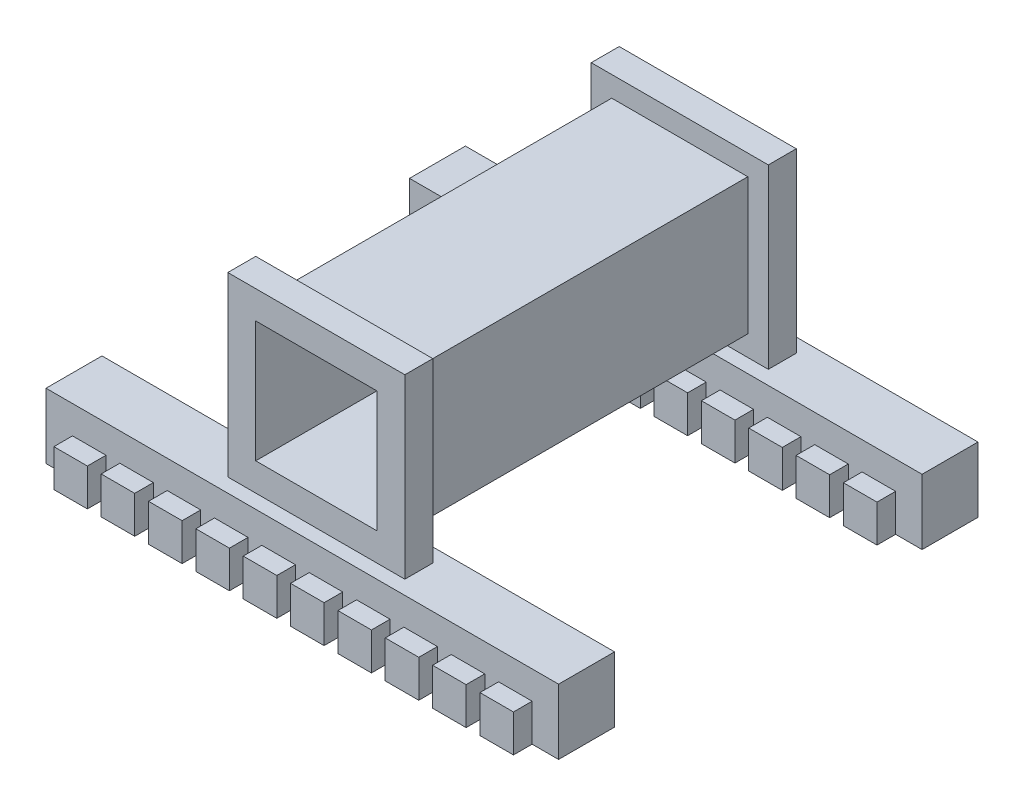
SolidWorks part; units mm, degrees
ref_plane "前视基准面" through (0, 0, 0) normal (0, 0, 1) x (1, 0, 0)
ref_plane "上视基准面" through (0, 0, 0) normal (0, 1, 0) x (1, 0, 0)
ref_plane "右视基准面" through (0, 0, 0) normal (1, 0, 0) x (0, 0, -1)
sketch "草图1" plane through (0, 0, 0) normal (0, 0, 1) x (1, 0, 0)
  line L0 (-9.5, 9.5) -> (9.5, 9.5)
  line L1 (-6.5, -6.5) -> (6.5, -6.5)
  line L2 (-6.5, -6.5) -> (-6.5, 6.5)
  line L3 (-6.5, 6.5) -> (6.5, 6.5)
  line L4 (6.5, -6.5) -> (6.5, 6.5)
  line L5 (-6.5, -6.5) -> (6.5, 6.5) construction
  line L6 (-6.5, 6.5) -> (6.5, -6.5) construction
  line L7 (9.5, -9.5) -> (9.5, 9.5)
  line L8 (-9.5, -9.5) -> (9.5, -9.5)
  line L9 (-9.5, -9.5) -> (-9.5, 9.5)
  line L10 (-7.3, 7.3) -> (7.3, 7.3)
  line L11 (7.3, -7.3) -> (7.3, 7.3)
  line L12 (-7.3, -7.3) -> (7.3, -7.3)
  line L13 (-7.3, -7.3) -> (-7.3, 7.3)
  line L15 (-27.5, -9.5) -> (27.5, -9.5)
  line L16 (-27.5, -9.5) -> (-27.5, -16.5)
  line L17 (-27.5, -16.5) -> (27.5, -16.5)
  line L18 (27.5, -9.5) -> (27.5, -16.5)
  point P0 (0, 0)
  dimension "D1" = 3
  dimension "D2" = 0.8
extrude "凸台-拉伸1" add sketch "草图1" along normal mid plane 42 contours L18 L15 L8 L16 L17 | L9 L8 L7 L0 L12 L13 L10 L11 | L13 L10 L11 L12 region at (0, 9.2313, 0) region at (0, -13, 0)
extrude "切除-拉伸1" cut sketch "草图1<3>" against normal mid plane 42 contours L2 L3 L4 L1
sketch "草图1<3>" plane through (0, 0, 0) normal (0, 0, 1) x (1, 0, 0) same geometry as "草图1"
sketch "草图2" plane through (0, 0, 0) normal (1, 0, 0) x (0, 0, -1)
  line L0 (21, -16.5) -> (21, -9.5) construction
  line L1 (21, -9.5) -> (-21, -9.5) construction
  line L2 (-21, -9.5) -> (-21, -16.5) construction
  line L3 (-21, -16.5) -> (21, -16.5) construction
  line L4 (21, -9.5) -> (21, 9.5) construction
  line L5 (21, 9.5) -> (-21, 9.5) construction
  line L6 (-21, 9.5) -> (-21, -9.5) construction
  line L7 (-21, -9.5) -> (21, -9.5) construction
  line L8 (21, -16.5) -> (21, -9.5)
  line L9 (21, -9.5) -> (-21, -9.5)
  line L10 (-21, -9.5) -> (-21, -16.5)
  line L11 (-21, -16.5) -> (21, -16.5)
  line L12 (21, -9.5) -> (21, 9.5)
  line L13 (21, 9.5) -> (-21, 9.5)
  line L14 (-21, 9.5) -> (-21, -9.5)
  line L15 (-21, -9.5) -> (21, -9.5)
extrude "切除-拉伸6" cut sketch "草图1<12>" against normal mid plane 36 contours L1 L4 L3 L2 | L9 L0 L7 L8 | L13 L10 L11 L12 region at (0, 0, 0)
sketch "草图1<12>" plane through (0, 0, 0) normal (0, 0, 1) x (1, 0, 0) same geometry as "草图1"
extrude "切除-拉伸7" cut sketch "草图1<13>" against normal mid plane 29 contours L18 L15 L8 L16 L17 region at (0, -13, 0)
sketch "草图1<13>" plane through (0, 0, 0) normal (0, 0, 1) x (1, 0, 0) same geometry as "草图1"
sketch "草图4" plane through (0, 0, 0) normal (1, 0, 0) x (0, 0, -1)
  line L0 (-21, -9.5) -> (-14.5, -9.5) construction
  line L1 (-14.5, -9.5) -> (-14.5, -16.5) construction
  line L2 (-14.5, -16.5) -> (-21, -16.5) construction
  line L3 (-21, -16.5) -> (-21, -9.5) construction
  line L4 (-18, 9.5) -> (-18, -9.5) construction
  line L5 (-18, -9.5) -> (-21, -9.5) construction
  line L6 (-21, -9.5) -> (-21, 9.5) construction
  line L7 (-21, 9.5) -> (-18, 9.5) construction
  line L8 (-18, -7.3) -> (-18, 7.3) construction
  line L9 (-18, 7.3) -> (18, 7.3) construction
  line L10 (18, 7.3) -> (18, -7.3) construction
  line L11 (18, -7.3) -> (-18, -7.3) construction
  line L12 (21, -9.5) -> (18, -9.5) construction
  line L13 (18, -9.5) -> (18, 9.5) construction
  line L14 (18, 9.5) -> (21, 9.5) construction
  line L15 (21, 9.5) -> (21, -9.5) construction
  line L16 (14.5, -16.5) -> (14.5, -9.5) construction
  line L17 (14.5, -9.5) -> (21, -9.5) construction
  line L18 (21, -9.5) -> (21, -16.5) construction
  line L19 (21, -16.5) -> (14.5, -16.5) construction
  line L20 (-21, -9.5) -> (-14.5, -9.5)
  line L21 (-14.5, -9.5) -> (-14.5, -16.5)
  line L22 (-14.5, -16.5) -> (-21, -16.5)
  line L23 (-21, -16.5) -> (-21, -9.5)
  line L24 (-18, 9.5) -> (-18, -9.5)
  line L25 (-18, -9.5) -> (-21, -9.5)
  line L26 (-21, -9.5) -> (-21, 9.5)
  line L27 (-21, 9.5) -> (-18, 9.5)
  line L28 (-18, -7.3) -> (-18, 7.3)
  line L29 (-18, 7.3) -> (18, 7.3)
  line L30 (18, 7.3) -> (18, -7.3)
  line L31 (18, -7.3) -> (-18, -7.3)
  line L32 (21, -9.5) -> (18, -9.5)
  line L33 (18, -9.5) -> (18, 9.5)
  line L34 (18, 9.5) -> (21, 9.5)
  line L35 (21, 9.5) -> (21, -9.5)
  line L36 (14.5, -16.5) -> (14.5, -9.5)
  line L37 (14.5, -9.5) -> (21, -9.5)
  line L38 (21, -9.5) -> (21, -16.5)
  line L39 (21, -16.5) -> (14.5, -16.5)
  line L40 (21, -9.5) -> (24.5, -9.5)
  line L41 (24.5, -9.5) -> (24.5, -16.5)
  line L42 (24.5, -16.5) -> (21, -16.5)
  line L43 (-21, -16.5) -> (-24.5049, -16.5)
  line L44 (-24.5049, -16.5) -> (-24.5049, -9.5)
  line L45 (-24.5049, -9.5) -> (-21, -9.5)
extrude "凸台-拉伸2" add sketch "草图4" along normal mid plane 55 contours L42 L41 L40 L38 | L45 L44 L43 L23 region at (0, -13, 22.7525) region at (0, -13, -22.75)
sketch "草图5" plane through (0, 0, -24.5) normal (0, 0, -1) x (-1, 0, 0)
  line L0 (-27.5, -16.5) -> (-22.86, -16.5)
  line L1 (-22.86, -16.5) -> (-22.86, -12.5036)
  line L3 (-17.78, -12.5036) -> (-17.78, -16.5)
  line L4 (27.5, -16.5) -> (27.5, -9.5)
  line L5 (27.5, -9.5) -> (-27.5, -9.5)
  line L6 (-27.5, -9.5) -> (-27.5, -16.5)
  line L7 (-27.5, -16.5) -> (27.5, -16.5)
  line L8 (27.5, -16.5) -> (27.5, -9.5)
  line L9 (27.5, -9.5) -> (-27.5, -9.5)
  line L10 (-27.5, -9.5) -> (-27.5, -16.5)
  line L12 (-9.5, -9.5) -> (9.5, -9.5)
  line L13 (-9.5, 9.5) -> (-9.5, -9.5)
  line L14 (9.5, 9.5) -> (-9.5, 9.5)
  line L15 (9.5, -9.5) -> (9.5, 9.5)
  line L16 (-9.5, -9.5) -> (9.5, -9.5)
  line L17 (-9.5, 9.5) -> (-9.5, -9.5)
  line L18 (9.5, 9.5) -> (-9.5, 9.5)
  line L19 (9.5, -9.5) -> (9.5, 9.5)
  line L20 (-17.78, -16.5) -> (-12.7, -16.5)
  line L21 (-12.7, -16.5) -> (-12.7, -12.5036)
  line L23 (-7.62, -12.5036) -> (-7.62, -16.5)
  line L24 (-27.5, -16.5) -> (27.5, -16.5) construction
  line L25 (-7.62, -16.5) -> (-2.54, -16.5)
  line L26 (-2.54, -16.5) -> (-2.54, -12.5186)
  line L28 (2.536, -12.5186) -> (2.536, -16.5)
  line L29 (2.536, -16.5) -> (7.62, -16.5)
  line L30 (7.62, -16.5) -> (7.62, -12.5078)
  line L32 (12.6981, -12.5078) -> (12.6981, -16.5)
  line L33 (12.6981, -16.5) -> (17.7801, -16.5)
  line L34 (17.7801, -16.5) -> (17.7801, -12.5082)
  line L36 (22.8591, -12.5082) -> (22.8591, -16.5)
  line L37 (22.8591, -16.5) -> (27.5, -16.5)
  line L39 (-21.06, -16.5) -> (-24.66, -16.5)
  line L40 (-21.06, -16.5) -> (-21.06, -12.5036)
  line L41 (-21.06, -12.5036) -> (-24.66, -12.5036)
  line L42 (-24.66, -16.5) -> (-24.66, -12.5036)
  line L43 (-21.06, -16.5) -> (-24.66, -12.5036) construction
  line L44 (-21.06, -12.5036) -> (-24.66, -16.5) construction
  line L45 (-15.98, -16.5) -> (-19.58, -16.5)
  line L46 (-15.98, -16.5) -> (-15.98, -12.5036)
  line L47 (-15.98, -12.5036) -> (-19.58, -12.5036)
  line L48 (-19.58, -16.5) -> (-19.58, -12.5036)
  line L49 (-15.98, -16.5) -> (-19.58, -12.5036) construction
  line L50 (-15.98, -12.5036) -> (-19.58, -16.5) construction
  line L51 (-10.9, -16.5) -> (-14.5, -16.5)
  line L52 (-10.9, -16.5) -> (-10.9, -12.5036)
  line L53 (-10.9, -12.5036) -> (-14.5, -12.5036)
  line L54 (-14.5, -16.5) -> (-14.5, -12.5036)
  line L55 (-10.9, -16.5) -> (-14.5, -12.5036) construction
  line L56 (-10.9, -12.5036) -> (-14.5, -16.5) construction
  line L57 (-5.82, -12.5036) -> (-9.42, -12.5036)
  line L58 (-5.82, -12.5036) -> (-5.82, -16.5)
  line L59 (-5.82, -16.5) -> (-9.42, -16.5)
  line L60 (-9.42, -12.5036) -> (-9.42, -16.5)
  line L61 (-5.82, -12.5036) -> (-9.42, -16.5) construction
  line L62 (-5.82, -16.5) -> (-9.42, -12.5036) construction
  line L63 (-0.74, -16.5075) -> (-4.34, -16.5075)
  line L64 (-0.74, -16.5075) -> (-0.74, -12.5111)
  line L65 (-0.74, -12.5111) -> (-4.34, -12.5111)
  line L66 (-4.34, -16.5075) -> (-4.34, -12.5111)
  line L67 (-0.74, -16.5075) -> (-4.34, -12.5111) construction
  line L68 (-0.74, -12.5111) -> (-4.34, -16.5075) construction
  line L69 (4.34, -16.5) -> (0.732, -16.5)
  line L70 (4.34, -16.5) -> (4.34, -12.5186)
  line L71 (4.34, -12.5186) -> (0.732, -12.5186)
  line L72 (0.732, -16.5) -> (0.732, -12.5186)
  line L73 (4.34, -16.5) -> (0.732, -12.5186) construction
  line L74 (4.34, -12.5186) -> (0.732, -16.5) construction
  line L75 (9.42, -16.4871) -> (5.82, -16.4871)
  line L76 (9.42, -16.4871) -> (9.42, -12.5206)
  line L77 (9.42, -12.5206) -> (5.82, -12.5206)
  line L78 (5.82, -16.4871) -> (5.82, -12.5206)
  line L79 (9.42, -16.4871) -> (5.82, -12.5206) construction
  line L80 (9.42, -12.5206) -> (5.82, -16.4871) construction
  line L81 (14.5, -16.5) -> (10.8963, -16.5)
  line L82 (14.5, -16.5) -> (14.5, -12.5078)
  line L83 (14.5, -12.5078) -> (10.8963, -12.5078)
  line L84 (10.8963, -16.5) -> (10.8963, -12.5078)
  line L85 (14.5, -16.5) -> (10.8963, -12.5078) construction
  line L86 (14.5, -12.5078) -> (10.8963, -16.5) construction
  line L87 (15.98, -16.5) -> (19.5801, -16.5)
  line L88 (15.98, -16.5) -> (15.98, -12.5082)
  line L89 (15.98, -12.5082) -> (19.5801, -12.5082)
  line L90 (19.5801, -16.5) -> (19.5801, -12.5082)
  line L91 (15.98, -16.5) -> (19.5801, -12.5082) construction
  line L92 (15.98, -12.5082) -> (19.5801, -16.5) construction
  line L93 (24.6583, -16.5) -> (21.06, -16.5)
  line L94 (24.6583, -16.5) -> (24.6583, -12.5082)
  line L95 (24.6583, -12.5082) -> (21.06, -12.5082)
  line L96 (21.06, -16.5) -> (21.06, -12.5082)
  line L97 (24.6583, -16.5) -> (21.06, -12.5082) construction
  line L98 (24.6583, -12.5082) -> (21.06, -16.5) construction
  point P6 (-22.86, -14.5018)
  point P35 (-17.78, -14.5018)
  point P40 (-12.7, -14.5018)
  point P45 (-7.62, -14.5018)
  point P50 (-2.54, -14.5093)
  point P55 (2.536, -14.5093)
  point P60 (7.62, -14.5039)
  point P65 (12.6981, -14.5039)
  point P70 (17.7801, -14.5041)
  point P75 (22.8591, -14.5041)
  line M42 (27.5, -16.5) -> (27.5, -9.5)
  line M43 (27.5, -9.5) -> (-27.5, -9.5)
  line M44 (-27.5, -9.5) -> (-27.5, -16.5)
  line M45 (-27.5, -16.5) -> (27.5, -16.5)
  dimension "D1" = 0
  dimension "D2" = 0
extrude "切除-拉伸9" cut sketch "草图5" against normal blind 2 contours L96 L95 L94 L37 L9 L42 L41 L40 L48 L47 L46 L20 L54 L53 L52 L60 L57 L58 L25 L66 L65 L64 L72 L71 L70 L29 L75 L78 L77 L76 M45 M42 M43 M44 region at (-0.0071, -12.1047, -24.5)
sketch "草图7" plane through (0, 0, 14.5) normal (0, 0, -1) x (-1, 0, 0)
  line L0 (21.06, -16.5) -> (24.6583, -16.5) construction
  line L1 (24.6583, -16.5) -> (24.6583, -12.5082) construction
  line L2 (24.6583, -12.5082) -> (21.06, -12.5082) construction
  line L3 (21.06, -12.5082) -> (21.06, -16.5) construction
  line L4 (15.98, -16.5) -> (19.5801, -16.5) construction
  line L5 (19.5801, -16.5) -> (19.5801, -12.5082) construction
  line L6 (19.5801, -12.5082) -> (15.98, -12.5082) construction
  line L7 (15.98, -12.5082) -> (15.98, -16.5) construction
  line L8 (10.8963, -16.5) -> (14.5, -16.5) construction
  line L9 (14.5, -16.5) -> (14.5, -12.5078) construction
  line L10 (14.5, -12.5078) -> (10.8963, -12.5078) construction
  line L11 (10.8963, -12.5078) -> (10.8963, -16.5) construction
  line L12 (5.82, -16.4871) -> (9.42, -16.4871) construction
  line L13 (9.42, -16.4871) -> (9.42, -12.5206) construction
  line L14 (9.42, -12.5206) -> (5.82, -12.5206) construction
  line L15 (5.82, -12.5206) -> (5.82, -16.4871) construction
  line L16 (0.732, -16.5) -> (4.34, -16.5) construction
  line L17 (4.34, -16.5) -> (4.34, -12.5186) construction
  line L18 (4.34, -12.5186) -> (0.732, -12.5186) construction
  line L19 (0.732, -12.5186) -> (0.732, -16.5) construction
  line L20 (-4.34, -16.5) -> (-0.74, -16.5) construction
  line L21 (-0.74, -16.5) -> (-0.74, -12.5111) construction
  line L22 (-0.74, -12.5111) -> (-4.34, -12.5111) construction
  line L23 (-4.34, -12.5111) -> (-4.34, -16.5) construction
  line L24 (-5.82, -16.5) -> (-5.82, -12.5036) construction
  line L25 (-5.82, -12.5036) -> (-9.42, -12.5036) construction
  line L26 (-9.42, -12.5036) -> (-9.42, -16.5) construction
  line L27 (-9.42, -16.5) -> (-5.82, -16.5) construction
  line L28 (-14.5, -16.5) -> (-10.9, -16.5) construction
  line L29 (-10.9, -16.5) -> (-10.9, -12.5036) construction
  line L30 (-10.9, -12.5036) -> (-14.5, -12.5036) construction
  line L31 (-14.5, -12.5036) -> (-14.5, -16.5) construction
  line L32 (-19.58, -16.5) -> (-15.98, -16.5) construction
  line L33 (-15.98, -16.5) -> (-15.98, -12.5036) construction
  line L34 (-15.98, -12.5036) -> (-19.58, -12.5036) construction
  line L35 (-19.58, -12.5036) -> (-19.58, -16.5) construction
  line L36 (-24.66, -16.5) -> (-21.06, -16.5) construction
  line L37 (-21.06, -16.5) -> (-21.06, -12.5036) construction
  line L38 (-21.06, -12.5036) -> (-24.66, -12.5036) construction
  line L39 (-24.66, -12.5036) -> (-24.66, -16.5) construction
  line L40 (21.06, -16.5) -> (24.6583, -16.5)
  line L41 (24.6583, -16.5) -> (24.6583, -12.5082)
  line L42 (24.6583, -12.5082) -> (21.06, -12.5082)
  line L43 (21.06, -12.5082) -> (21.06, -16.5)
  line L44 (15.98, -16.5) -> (19.5801, -16.5)
  line L45 (19.5801, -16.5) -> (19.5801, -12.5082)
  line L46 (19.5801, -12.5082) -> (15.98, -12.5082)
  line L47 (15.98, -12.5082) -> (15.98, -16.5)
  line L48 (10.8963, -16.5) -> (14.5, -16.5)
  line L49 (14.5, -16.5) -> (14.5, -12.5078)
  line L50 (14.5, -12.5078) -> (10.8963, -12.5078)
  line L51 (10.8963, -12.5078) -> (10.8963, -16.5)
  line L52 (5.82, -16.4871) -> (9.42, -16.4871)
  line L53 (9.42, -16.4871) -> (9.42, -12.5206)
  line L54 (9.42, -12.5206) -> (5.82, -12.5206)
  line L55 (5.82, -12.5206) -> (5.82, -16.4871)
  line L56 (0.732, -16.5) -> (4.34, -16.5)
  line L57 (4.34, -16.5) -> (4.34, -12.5186)
  line L58 (4.34, -12.5186) -> (0.732, -12.5186)
  line L59 (0.732, -12.5186) -> (0.732, -16.5)
  line L60 (-4.34, -16.5) -> (-0.74, -16.5)
  line L61 (-0.74, -16.5) -> (-0.74, -12.5111)
  line L62 (-0.74, -12.5111) -> (-4.34, -12.5111)
  line L63 (-4.34, -12.5111) -> (-4.34, -16.5)
  line L64 (-5.82, -16.5) -> (-5.82, -12.5036)
  line L65 (-5.82, -12.5036) -> (-9.42, -12.5036)
  line L66 (-9.42, -12.5036) -> (-9.42, -16.5)
  line L67 (-9.42, -16.5) -> (-5.82, -16.5)
  line L68 (-14.5, -16.5) -> (-10.9, -16.5)
  line L69 (-10.9, -16.5) -> (-10.9, -12.5036)
  line L70 (-10.9, -12.5036) -> (-14.5, -12.5036)
  line L71 (-14.5, -12.5036) -> (-14.5, -16.5)
  line L72 (-19.58, -16.5) -> (-15.98, -16.5)
  line L73 (-15.98, -16.5) -> (-15.98, -12.5036)
  line L74 (-15.98, -12.5036) -> (-19.58, -12.5036)
  line L75 (-19.58, -12.5036) -> (-19.58, -16.5)
  line L76 (-24.66, -16.5) -> (-21.06, -16.5)
  line L77 (-21.06, -16.5) -> (-21.06, -12.5036)
  line L78 (-21.06, -12.5036) -> (-24.66, -12.5036)
  line L79 (-24.66, -12.5036) -> (-24.66, -16.5)
  line L120 (19.5801, -16.5) -> (21.06, -16.5)
  line L121 (21.06, -16.5) -> (21.06, -12.5082)
  line L122 (21.06, -12.5082) -> (24.6583, -12.5082)
  line L123 (24.6583, -12.5082) -> (24.6583, -16.5)
  line L124 (24.6583, -16.5) -> (27.5, -16.5)
  line L125 (27.5, -16.5) -> (27.5, -9.5)
  line L126 (27.5, -9.5) -> (-27.5, -9.5)
  line L127 (-27.5, -9.5) -> (-27.5, -16.5)
  line L128 (-27.5, -16.5) -> (-24.66, -16.5)
  line L129 (-24.66, -16.5) -> (-24.66, -12.5036)
  line L130 (-24.66, -12.5036) -> (-21.06, -12.5036)
  line L131 (-21.06, -12.5036) -> (-21.06, -16.5)
  line L132 (-21.06, -16.5) -> (-19.58, -16.5)
  line L133 (-19.58, -16.5) -> (-19.58, -12.5036)
  line L134 (-19.58, -12.5036) -> (-15.98, -12.5036)
  line L135 (-15.98, -12.5036) -> (-15.98, -16.5)
  line L136 (-15.98, -16.5) -> (-14.5, -16.5)
  line L137 (-14.5, -16.5) -> (-14.5, -12.5036)
  line L138 (-14.5, -12.5036) -> (-10.9, -12.5036)
  line L139 (-10.9, -12.5036) -> (-10.9, -16.5)
  line L140 (-10.9, -16.5) -> (-9.42, -16.5)
  line L141 (-9.42, -16.5) -> (-9.42, -12.5036)
  line L142 (-9.42, -12.5036) -> (-5.82, -12.5036)
  line L143 (-5.82, -12.5036) -> (-5.82, -16.5)
  line L144 (-5.82, -16.5) -> (-4.34, -16.5)
  line L145 (-4.34, -16.5) -> (-4.34, -12.5111)
  line L146 (-4.34, -12.5111) -> (-0.74, -12.5111)
  line L147 (-0.74, -12.5111) -> (-0.74, -16.5)
  line L148 (-0.74, -16.5) -> (0.732, -16.5)
  line L149 (0.732, -16.5) -> (0.732, -12.5186)
  line L150 (0.732, -12.5186) -> (4.34, -12.5186)
  line L151 (4.34, -12.5186) -> (4.34, -16.5)
  line L152 (4.34, -16.5) -> (10.8963, -16.5)
  line L153 (10.8963, -16.5) -> (10.8963, -12.5078)
  line L154 (10.8963, -12.5078) -> (14.5, -12.5078)
  line L155 (14.5, -12.5078) -> (14.5, -16.5)
  line L156 (14.5, -16.5) -> (15.98, -16.5)
  line L157 (15.98, -16.5) -> (15.98, -12.5082)
  line L158 (15.98, -12.5082) -> (19.5801, -12.5082)
  line L159 (19.5801, -12.5082) -> (19.5801, -16.5)
  line L160 (19.5801, -16.5) -> (21.06, -16.5)
  line L161 (21.06, -16.5) -> (21.06, -12.5082)
  line L162 (21.06, -12.5082) -> (24.6583, -12.5082)
  line L163 (24.6583, -12.5082) -> (24.6583, -16.5)
  line L164 (24.6583, -16.5) -> (27.5, -16.5)
  line L165 (27.5, -16.5) -> (27.5, -9.5)
  line L166 (27.5, -9.5) -> (-27.5, -9.5)
  line L167 (-27.5, -9.5) -> (-27.5, -16.5)
  line L168 (-27.5, -16.5) -> (-24.66, -16.5)
  line L169 (-24.66, -16.5) -> (-24.66, -12.5036)
  line L170 (-24.66, -12.5036) -> (-21.06, -12.5036)
  line L171 (-21.06, -12.5036) -> (-21.06, -16.5)
  line L172 (-21.06, -16.5) -> (-19.58, -16.5)
  line L173 (-19.58, -16.5) -> (-19.58, -12.5036)
  line L174 (-19.58, -12.5036) -> (-15.98, -12.5036)
  line L175 (-15.98, -12.5036) -> (-15.98, -16.5)
  line L176 (-15.98, -16.5) -> (-14.5, -16.5)
  line L177 (-14.5, -16.5) -> (-14.5, -12.5036)
  line L178 (-14.5, -12.5036) -> (-10.9, -12.5036)
  line L179 (-10.9, -12.5036) -> (-10.9, -16.5)
  line L180 (-10.9, -16.5) -> (-9.42, -16.5)
  line L181 (-9.42, -16.5) -> (-9.42, -12.5036)
  line L182 (-9.42, -12.5036) -> (-5.82, -12.5036)
  line L183 (-5.82, -12.5036) -> (-5.82, -16.5)
  line L184 (-5.82, -16.5) -> (-4.34, -16.5)
  line L185 (-4.34, -16.5) -> (-4.34, -12.5111)
  line L186 (-4.34, -12.5111) -> (-0.74, -12.5111)
  line L187 (-0.74, -12.5111) -> (-0.74, -16.5)
  line L188 (-0.74, -16.5) -> (0.732, -16.5)
  line L189 (0.732, -16.5) -> (0.732, -12.5186)
  line L190 (0.732, -12.5186) -> (4.34, -12.5186)
  line L191 (4.34, -12.5186) -> (4.34, -16.5)
  line L192 (4.34, -16.5) -> (10.8963, -16.5)
  line L193 (10.8963, -16.5) -> (10.8963, -12.5078)
  line L194 (10.8963, -12.5078) -> (14.5, -12.5078)
  line L195 (14.5, -12.5078) -> (14.5, -16.5)
  line L196 (14.5, -16.5) -> (15.98, -16.5)
  line L197 (15.98, -16.5) -> (15.98, -12.5082)
  line L198 (15.98, -12.5082) -> (19.5801, -12.5082)
  line L199 (19.5801, -12.5082) -> (19.5801, -16.5)
  line M1 (-27.5, -9.5) -> (-27.5, -16.5)
  line M2 (-27.5, -16.5) -> (27.5, -16.5)
  line M3 (27.5, -16.5) -> (27.5, -9.5)
  line M4 (27.5, -9.5) -> (-27.5, -9.5)
  dimension "D1" = 0
extrude "切除-拉伸10" cut sketch "草图7" against normal blind 2 contours L79 L78 L77 L75 L74 L73 L71 L70 L69 L66 L65 L64 L63 L62 L61 L59 L58 L57 L51 L50 L49 L47 L46 L45 L43 L42 L41 L55 L54 L53 L52 M2 M3 M4 M1 region at (-0.0071, -12.1047, 14.5)
sketch "草图9" plane through (0, 0, -14.5) normal (0, 0, 1) x (1, 0, 0)
  line L0 (-4.34, -16.5) -> (-4.34, -12.5186) construction
  line L1 (-4.34, -12.5186) -> (-0.732, -12.5186) construction
  line L2 (-0.732, -12.5186) -> (-0.732, -16.5) construction
  line L3 (-0.732, -16.5) -> (-4.34, -16.5) construction
  line L4 (27.5, -16.5) -> (27.5, -9.5)
  line L5 (27.5, -9.5) -> (-27.5, -9.5)
  line L6 (-27.5, -9.5) -> (-27.5, -16.5)
  line L7 (-27.5, -16.5) -> (27.5, -16.5)
  line L8 (27.5, -16.5) -> (27.5, -9.5)
  line L9 (27.5, -9.5) -> (-27.5, -9.5)
  line L10 (-27.5, -9.5) -> (-27.5, -16.5)
  line L11 (-27.5, -16.5) -> (27.5, -16.5)
  line L12 (-5.82, -12.5206) -> (-5.82, -16.4871) construction
  line L13 (-5.82, -16.4871) -> (-9.42, -16.4871) construction
  line L14 (-9.42, -16.4871) -> (-9.42, -12.5206) construction
  line L15 (-9.42, -12.5206) -> (-5.82, -12.5206) construction
  line L16 (-14.5, -16.5) -> (-14.5, -12.5078) construction
  line L17 (-14.5, -12.5078) -> (-10.8963, -12.5078) construction
  line L18 (-10.8963, -12.5078) -> (-10.8963, -16.5) construction
  line L19 (-10.8963, -16.5) -> (-14.5, -16.5) construction
  line L20 (-19.5801, -16.5) -> (-19.5801, -12.5082) construction
  line L21 (-19.5801, -12.5082) -> (-15.98, -12.5082) construction
  line L22 (-15.98, -12.5082) -> (-15.98, -16.5) construction
  line L23 (-15.98, -16.5) -> (-19.5801, -16.5) construction
  line L24 (-24.6583, -16.5) -> (-24.6583, -12.5082) construction
  line L25 (-24.6583, -12.5082) -> (-21.06, -12.5082) construction
  line L26 (-21.06, -12.5082) -> (-21.06, -16.5) construction
  line L27 (-21.06, -16.5) -> (-24.6583, -16.5) construction
  line L28 (0.74, -16.5) -> (0.74, -12.5111) construction
  line L29 (0.74, -12.5111) -> (4.34, -12.5111) construction
  line L30 (4.34, -12.5111) -> (4.34, -16.5) construction
  line L31 (4.34, -16.5) -> (0.74, -16.5) construction
  line L32 (5.82, -16.5) -> (5.82, -12.5036) construction
  line L33 (5.82, -12.5036) -> (9.42, -12.5036) construction
  line L34 (9.42, -12.5036) -> (9.42, -16.5) construction
  line L35 (9.42, -16.5) -> (5.82, -16.5) construction
  line L36 (10.9, -16.5) -> (10.9, -12.5036) construction
  line L37 (10.9, -12.5036) -> (14.5, -12.5036) construction
  line L38 (14.5, -12.5036) -> (14.5, -16.5) construction
  line L39 (14.5, -16.5) -> (10.9, -16.5) construction
  line L40 (15.98, -16.5) -> (15.98, -12.5036) construction
  line L41 (15.98, -12.5036) -> (19.58, -12.5036) construction
  line L42 (19.58, -12.5036) -> (19.58, -16.5) construction
  line L43 (19.58, -16.5) -> (15.98, -16.5) construction
  line L44 (24.66, -12.5036) -> (24.66, -16.5) construction
  line L45 (24.66, -16.5) -> (21.06, -16.5) construction
  line L46 (21.06, -16.5) -> (21.06, -12.5036) construction
  line L47 (21.06, -12.5036) -> (24.66, -12.5036) construction
  line L48 (-4.34, -16.5) -> (-4.34, -12.5186)
  line L49 (-4.34, -12.5186) -> (-0.732, -12.5186)
  line L50 (-0.732, -12.5186) -> (-0.732, -16.5)
  line L51 (-0.732, -16.5) -> (-4.34, -16.5)
  line L52 (-5.82, -12.5206) -> (-5.82, -16.4871)
  line L53 (-5.82, -16.4871) -> (-9.42, -16.4871)
  line L54 (-9.42, -16.4871) -> (-9.42, -12.5206)
  line L55 (-9.42, -12.5206) -> (-5.82, -12.5206)
  line L56 (-14.5, -16.5) -> (-14.5, -12.5078)
  line L57 (-14.5, -12.5078) -> (-10.8963, -12.5078)
  line L58 (-10.8963, -12.5078) -> (-10.8963, -16.5)
  line L59 (-10.8963, -16.5) -> (-14.5, -16.5)
  line L60 (-19.5801, -16.5) -> (-19.5801, -12.5082)
  line L61 (-19.5801, -12.5082) -> (-15.98, -12.5082)
  line L62 (-15.98, -12.5082) -> (-15.98, -16.5)
  line L63 (-15.98, -16.5) -> (-19.5801, -16.5)
  line L64 (-24.6583, -16.5) -> (-24.6583, -12.5082)
  line L65 (-24.6583, -12.5082) -> (-21.06, -12.5082)
  line L66 (-21.06, -12.5082) -> (-21.06, -16.5)
  line L67 (-21.06, -16.5) -> (-24.6583, -16.5)
  line L68 (0.74, -16.5) -> (0.74, -12.5111)
  line L69 (0.74, -12.5111) -> (4.34, -12.5111)
  line L70 (4.34, -12.5111) -> (4.34, -16.5)
  line L71 (4.34, -16.5) -> (0.74, -16.5)
  line L72 (5.82, -16.5) -> (5.82, -12.5036)
  line L73 (5.82, -12.5036) -> (9.42, -12.5036)
  line L74 (9.42, -12.5036) -> (9.42, -16.5)
  line L75 (9.42, -16.5) -> (5.82, -16.5)
  line L76 (10.9, -16.5) -> (10.9, -12.5036)
  line L77 (10.9, -12.5036) -> (14.5, -12.5036)
  line L78 (14.5, -12.5036) -> (14.5, -16.5)
  line L79 (14.5, -16.5) -> (10.9, -16.5)
  line L80 (15.98, -16.5) -> (15.98, -12.5036)
  line L81 (15.98, -12.5036) -> (19.58, -12.5036)
  line L82 (19.58, -12.5036) -> (19.58, -16.5)
  line L83 (19.58, -16.5) -> (15.98, -16.5)
  line L84 (24.66, -12.5036) -> (24.66, -16.5)
  line L85 (24.66, -16.5) -> (21.06, -16.5)
  line L86 (21.06, -16.5) -> (21.06, -12.5036)
  line L87 (21.06, -12.5036) -> (24.66, -12.5036)
  line M5 (27.5, -16.5) -> (27.5, -9.5)
  line M6 (27.5, -9.5) -> (-27.5, -9.5)
  line M7 (-27.5, -9.5) -> (-27.5, -16.5)
  line M8 (-27.5, -16.5) -> (27.5, -16.5)
  dimension "D1" = 0
sketch "草图10" plane through (0, 0, 24.5049) normal (0, 0, 1) x (1, 0, 0)
  line L0 (-21.06, -16.5) -> (-24.6583, -16.5) construction
  line L1 (-24.6583, -16.5) -> (-24.6583, -12.5082) construction
  line L2 (-24.6583, -12.5082) -> (-21.06, -12.5082) construction
  line L3 (-21.06, -12.5082) -> (-21.06, -16.5) construction
  line L4 (-27.5, -9.5) -> (-27.5, -16.5)
  line L5 (-27.5, -16.5) -> (27.5, -16.5)
  line L6 (27.5, -16.5) -> (27.5, -9.5)
  line L7 (27.5, -9.5) -> (-27.5, -9.5)
  line L8 (-27.5, -9.5) -> (-27.5, -16.5)
  line L9 (-27.5, -16.5) -> (27.5, -16.5)
  line L10 (27.5, -16.5) -> (27.5, -9.5)
  line L11 (27.5, -9.5) -> (-27.5, -9.5)
  line L12 (-15.98, -16.5) -> (-19.5801, -16.5) construction
  line L13 (-19.5801, -16.5) -> (-19.5801, -12.5082) construction
  line L14 (-19.5801, -12.5082) -> (-15.98, -12.5082) construction
  line L15 (-15.98, -12.5082) -> (-15.98, -16.5) construction
  line L16 (-10.8963, -16.5) -> (-14.5, -16.5) construction
  line L17 (-14.5, -16.5) -> (-14.5, -12.5078) construction
  line L18 (-14.5, -12.5078) -> (-10.8963, -12.5078) construction
  line L19 (-10.8963, -12.5078) -> (-10.8963, -16.5) construction
  line L20 (-5.82, -16.4871) -> (-9.42, -16.4871) construction
  line L21 (-9.42, -16.4871) -> (-9.42, -12.5206) construction
  line L22 (-9.42, -12.5206) -> (-5.82, -12.5206) construction
  line L23 (-5.82, -12.5206) -> (-5.82, -16.4871) construction
  line L24 (-0.732, -16.5) -> (-4.34, -16.5) construction
  line L25 (-4.34, -16.5) -> (-4.34, -12.5186) construction
  line L26 (-4.34, -12.5186) -> (-0.732, -12.5186) construction
  line L27 (-0.732, -12.5186) -> (-0.732, -16.5) construction
  line L28 (4.34, -16.5) -> (0.74, -16.5) construction
  line L29 (0.74, -16.5) -> (0.74, -12.5111) construction
  line L30 (0.74, -12.5111) -> (4.34, -12.5111) construction
  line L31 (4.34, -12.5111) -> (4.34, -16.5) construction
  line L32 (5.82, -16.5) -> (5.82, -12.5036) construction
  line L33 (5.82, -12.5036) -> (9.42, -12.5036) construction
  line L34 (9.42, -12.5036) -> (9.42, -16.5) construction
  line L35 (9.42, -16.5) -> (5.82, -16.5) construction
  line L36 (14.5, -16.5) -> (10.9, -16.5) construction
  line L37 (10.9, -16.5) -> (10.9, -12.5036) construction
  line L38 (10.9, -12.5036) -> (14.5, -12.5036) construction
  line L39 (14.5, -12.5036) -> (14.5, -16.5) construction
  line L40 (19.58, -16.5) -> (15.98, -16.5) construction
  line L41 (15.98, -16.5) -> (15.98, -12.5036) construction
  line L42 (15.98, -12.5036) -> (19.58, -12.5036) construction
  line L43 (19.58, -12.5036) -> (19.58, -16.5) construction
  line L44 (24.66, -16.5) -> (21.06, -16.5) construction
  line L45 (21.06, -16.5) -> (21.06, -12.5036) construction
  line L46 (21.06, -12.5036) -> (24.66, -12.5036) construction
  line L47 (24.66, -12.5036) -> (24.66, -16.5) construction
  line L48 (-21.06, -16.5) -> (-24.6583, -16.5)
  line L49 (-24.6583, -16.5) -> (-24.6583, -12.5082)
  line L50 (-24.6583, -12.5082) -> (-21.06, -12.5082)
  line L51 (-21.06, -12.5082) -> (-21.06, -16.5)
  line L52 (-15.98, -16.5) -> (-19.5801, -16.5)
  line L53 (-19.5801, -16.5) -> (-19.5801, -12.5082)
  line L54 (-19.5801, -12.5082) -> (-15.98, -12.5082)
  line L55 (-15.98, -12.5082) -> (-15.98, -16.5)
  line L56 (-10.8963, -16.5) -> (-14.5, -16.5)
  line L57 (-14.5, -16.5) -> (-14.5, -12.5078)
  line L58 (-14.5, -12.5078) -> (-10.8963, -12.5078)
  line L59 (-10.8963, -12.5078) -> (-10.8963, -16.5)
  line L60 (-5.82, -16.4871) -> (-9.42, -16.4871)
  line L61 (-9.42, -16.4871) -> (-9.42, -12.5206)
  line L62 (-9.42, -12.5206) -> (-5.82, -12.5206)
  line L63 (-5.82, -12.5206) -> (-5.82, -16.4871)
  line L64 (-0.732, -16.5) -> (-4.34, -16.5)
  line L65 (-4.34, -16.5) -> (-4.34, -12.5186)
  line L66 (-4.34, -12.5186) -> (-0.732, -12.5186)
  line L67 (-0.732, -12.5186) -> (-0.732, -16.5)
  line L68 (4.34, -16.5) -> (0.74, -16.5)
  line L69 (0.74, -16.5) -> (0.74, -12.5111)
  line L70 (0.74, -12.5111) -> (4.34, -12.5111)
  line L71 (4.34, -12.5111) -> (4.34, -16.5)
  line L72 (5.82, -16.5) -> (5.82, -12.5036)
  line L73 (5.82, -12.5036) -> (9.42, -12.5036)
  line L74 (9.42, -12.5036) -> (9.42, -16.5)
  line L75 (9.42, -16.5) -> (5.82, -16.5)
  line L76 (14.5, -16.5) -> (10.9, -16.5)
  line L77 (10.9, -16.5) -> (10.9, -12.5036)
  line L78 (10.9, -12.5036) -> (14.5, -12.5036)
  line L79 (14.5, -12.5036) -> (14.5, -16.5)
  line L80 (19.58, -16.5) -> (15.98, -16.5)
  line L81 (15.98, -16.5) -> (15.98, -12.5036)
  line L82 (15.98, -12.5036) -> (19.58, -12.5036)
  line L83 (19.58, -12.5036) -> (19.58, -16.5)
  line L84 (24.66, -16.5) -> (21.06, -16.5)
  line L85 (21.06, -16.5) -> (21.06, -12.5036)
  line L86 (21.06, -12.5036) -> (24.66, -12.5036)
  line L87 (24.66, -12.5036) -> (24.66, -16.5)
  line M5 (-27.5, -9.5) -> (-27.5, -16.5)
  line M6 (-27.5, -16.5) -> (27.5, -16.5)
  line M7 (27.5, -16.5) -> (27.5, -9.5)
  line M8 (27.5, -9.5) -> (-27.5, -9.5)
  dimension "D1" = 0
extrude "切除-拉伸11" cut sketch "草图9" against normal blind 2 contours L86 L87 L84 L11 L64 L65 L66 L60 L61 L62 L56 L57 L58 L48 L49 L50 L68 L69 L70 L72 L73 L74 L76 L77 L78 L80 L81 L82 L54 L55 L52 L53 M5 M6 M7 M8 region at (-0.0071, -12.1047, -14.5)
extrude "切除-拉伸12" cut sketch "草图10" against normal blind 2 contours L86 L87 L49 L50 L51 L53 L54 L55 L57 L58 L59 L65 L66 L67 L69 L70 L71 L72 L73 L74 L77 L78 L79 L81 L82 L83 L85 L62 L63 L60 L61 M6 M7 M8 M5 region at (-0.0071, -12.1047, 24.5049)
sketch "草图11" plane through (0, -16.5, 0) normal (0, -1, 0) x (1, 0, 0)
  line L0 (-22.8591, 14.5) -> (-22.8591, 24.5049)
  line L1 (-17.7801, 14.5) -> (-17.7801, 24.5049)
  line L2 (-12.6981, 14.5) -> (-12.6981, 24.5049)
  line L3 (-7.62, 14.5) -> (-7.62, 24.5049)
  line L4 (-5.82, -14.5) -> (-9.42, -14.5)
  line L5 (-9.42, -14.5) -> (-9.42, -16.5)
  line L6 (-9.42, -16.5) -> (-5.82, -16.5)
  line L7 (-5.82, -16.5) -> (-5.82, -14.5)
  line L8 (-5.82, -14.5) -> (-9.42, -14.5)
  line L9 (-9.42, -14.5) -> (-9.42, -16.5)
  line L10 (-9.42, -16.5) -> (-5.82, -16.5)
  line L11 (-5.82, -16.5) -> (-5.82, -14.5)
  line L12 (-9.42, -24.5) -> (-5.82, -24.5)
  line L13 (-5.82, -24.5) -> (-5.82, -22.5)
  line L14 (-5.82, -22.5) -> (-9.42, -22.5)
  line L15 (-9.42, -22.5) -> (-9.42, -24.5)
  line L16 (-9.42, -24.5) -> (-5.82, -24.5)
  line L17 (-5.82, -24.5) -> (-5.82, -22.5)
  line L18 (-5.82, -22.5) -> (-9.42, -22.5)
  line L19 (-9.42, -22.5) -> (-9.42, -24.5)
  line L20 (-9.42, 14.5) -> (-5.82, 14.5)
  line L21 (-5.82, 14.5) -> (-5.82, 16.5)
  line L22 (-5.82, 16.5) -> (-9.42, 16.5)
  line L23 (-9.42, 16.5) -> (-9.42, 14.5)
  line L24 (-9.42, 14.5) -> (-5.82, 14.5)
  line L25 (-5.82, 14.5) -> (-5.82, 16.5)
  line L27 (-9.42, 16.5) -> (-9.42, 14.5)
  line L28 (-5.82, 24.5049) -> (-9.42, 24.5049)
  line L29 (-9.42, 24.5049) -> (-9.42, 22.5049)
  line L30 (-9.42, 22.5049) -> (-5.82, 22.5049)
  line L31 (-5.82, 22.5049) -> (-5.82, 24.5049)
  line L32 (-5.82, 24.5049) -> (-9.42, 24.5049)
  line L33 (-9.42, 24.5049) -> (-9.42, 22.5049)
  line L35 (-5.82, 22.5049) -> (-5.82, 24.5049)
  line L36 (-2.536, 14.5) -> (-2.536, 24.5049)
  line L37 (2.54, 14.5) -> (2.54, 24.5049)
  line L38 (7.62, 14.5) -> (7.62, 24.5049)
  line L39 (12.7, 14.5) -> (12.7, 24.5049)
  line L40 (17.78, 14.5) -> (17.78, 24.5049)
  line L41 (22.86, 14.5) -> (22.86, 24.5049)
  line L42 (22.86, -24.5) -> (22.86, -14.5)
  line L43 (17.78, -24.5) -> (17.78, -14.5)
  line L44 (12.7, -24.5) -> (12.7, -14.5)
  line L45 (2.54, -24.5) -> (2.54, -14.5)
  line L46 (7.62, -24.5) -> (7.62, -14.5)
  line L47 (-2.536, -24.5) -> (-2.536, -14.5)
  line L48 (-7.62, -24.5) -> (-7.62, -14.5)
  line L49 (-12.6981, -24.5) -> (-12.6981, -14.5)
  line L50 (-17.7801, -24.5) -> (-17.7801, -14.5)
  line L51 (-22.8591, -24.5) -> (-22.8591, -14.5)
  line L76 (-21.06, -14.5) -> (-24.6583, -14.5)
  line L77 (-24.6583, -14.5) -> (-24.6583, -16.5)
  line L78 (-24.6583, -16.5) -> (-27.5, -16.5)
  line L79 (-27.5, -16.5) -> (-27.5, -22.5)
  line L80 (-27.5, -22.5) -> (-24.6583, -22.5)
  line L81 (-24.6583, -22.5) -> (-24.6583, -24.5)
  line L82 (-24.6583, -24.5) -> (-21.06, -24.5)
  line L83 (-21.06, -24.5) -> (-21.06, -22.5)
  line L84 (-21.06, -22.5) -> (-19.5801, -22.5)
  line L85 (-19.5801, -22.5) -> (-19.5801, -24.5)
  line L86 (-19.5801, -24.5) -> (-15.98, -24.5)
  line L87 (-15.98, -24.5) -> (-15.98, -22.5)
  line L88 (-15.98, -22.5) -> (-14.5, -22.5)
  line L89 (-14.5, -22.5) -> (-14.5, -24.5)
  line L90 (-14.5, -24.5) -> (-10.8963, -24.5)
  line L91 (-10.8963, -24.5) -> (-10.8963, -22.5)
  line L92 (-10.8963, -22.5) -> (-4.34, -22.5)
  line L93 (-4.34, -22.5) -> (-4.34, -24.5)
  line L94 (-4.34, -24.5) -> (-0.732, -24.5)
  line L95 (-0.732, -24.5) -> (-0.732, -22.5)
  line L96 (-0.732, -22.5) -> (0.74, -22.5)
  line L97 (0.74, -22.5) -> (0.74, -24.5)
  line L98 (0.74, -24.5) -> (4.34, -24.5)
  line L99 (4.34, -24.5) -> (4.34, -22.5)
  line L100 (4.34, -22.5) -> (5.82, -22.5)
  line L101 (5.82, -22.5) -> (5.82, -24.5)
  line L102 (5.82, -24.5) -> (9.42, -24.5)
  line L103 (9.42, -24.5) -> (9.42, -22.5)
  line L104 (9.42, -22.5) -> (10.9, -22.5)
  line L105 (10.9, -22.5) -> (10.9, -24.5)
  line L106 (10.9, -24.5) -> (14.5, -24.5)
  line L107 (14.5, -24.5) -> (14.5, -22.5)
  line L108 (14.5, -22.5) -> (15.98, -22.5)
  line L109 (15.98, -22.5) -> (15.98, -24.5)
  line L110 (15.98, -24.5) -> (19.58, -24.5)
  line L111 (19.58, -24.5) -> (19.58, -22.5)
  line L112 (19.58, -22.5) -> (21.06, -22.5)
  line L113 (21.06, -22.5) -> (21.06, -24.5)
  line L114 (21.06, -24.5) -> (24.66, -24.5)
  line L115 (24.66, -24.5) -> (24.66, -22.5)
  line L116 (24.66, -22.5) -> (27.5, -22.5)
  line L117 (27.5, -22.5) -> (27.5, -16.5)
  line L118 (27.5, -16.5) -> (24.66, -16.5)
  line L119 (24.66, -16.5) -> (24.66, -14.5)
  line L120 (24.66, -14.5) -> (21.06, -14.5)
  line L121 (21.06, -14.5) -> (21.06, -16.5)
  line L122 (21.06, -16.5) -> (19.58, -16.5)
  line L123 (19.58, -16.5) -> (19.58, -14.5)
  line L124 (19.58, -14.5) -> (15.98, -14.5)
  line L125 (15.98, -14.5) -> (15.98, -16.5)
  line L126 (15.98, -16.5) -> (14.5, -16.5)
  line L127 (14.5, -16.5) -> (14.5, -14.5)
  line L128 (14.5, -14.5) -> (10.9, -14.5)
  line L129 (10.9, -14.5) -> (10.9, -16.5)
  line L130 (10.9, -16.5) -> (9.42, -16.5)
  line L131 (9.42, -16.5) -> (9.42, -14.5)
  line L132 (9.42, -14.5) -> (5.82, -14.5)
  line L133 (5.82, -14.5) -> (5.82, -16.5)
  line L134 (5.82, -16.5) -> (4.34, -16.5)
  line L135 (4.34, -16.5) -> (4.34, -14.5)
  line L136 (4.34, -14.5) -> (0.74, -14.5)
  line L137 (0.74, -14.5) -> (0.74, -16.5)
  line L138 (0.74, -16.5) -> (-0.732, -16.5)
  line L139 (-0.732, -16.5) -> (-0.732, -14.5)
  line L140 (-0.732, -14.5) -> (-4.34, -14.5)
  line L141 (-4.34, -14.5) -> (-4.34, -16.5)
  line L142 (-4.34, -16.5) -> (-10.8963, -16.5)
  line L143 (-10.8963, -16.5) -> (-10.8963, -14.5)
  line L144 (-10.8963, -14.5) -> (-14.5, -14.5)
  line L145 (-14.5, -14.5) -> (-14.5, -16.5)
  line L146 (-14.5, -16.5) -> (-15.98, -16.5)
  line L147 (-15.98, -16.5) -> (-15.98, -14.5)
  line L148 (-15.98, -14.5) -> (-19.5801, -14.5)
  line L149 (-19.5801, -14.5) -> (-19.5801, -16.5)
  line L150 (-19.5801, -16.5) -> (-21.06, -16.5)
  line L151 (-21.06, -16.5) -> (-21.06, -14.5)
  line L152 (-21.06, -14.5) -> (-24.6583, -14.5)
  line L153 (-24.6583, -14.5) -> (-24.6583, -16.5)
  line L154 (-24.6583, -16.5) -> (-27.5, -16.5)
  line L155 (-27.5, -16.5) -> (-27.5, -22.5)
  line L156 (-27.5, -22.5) -> (-24.6583, -22.5)
  line L157 (-24.6583, -22.5) -> (-24.6583, -24.5)
  line L158 (-24.6583, -24.5) -> (-21.06, -24.5)
  line L159 (-21.06, -24.5) -> (-21.06, -22.5)
  line L160 (-21.06, -22.5) -> (-19.5801, -22.5)
  line L161 (-19.5801, -22.5) -> (-19.5801, -24.5)
  line L162 (-19.5801, -24.5) -> (-15.98, -24.5)
  line L163 (-15.98, -24.5) -> (-15.98, -22.5)
  line L164 (-15.98, -22.5) -> (-14.5, -22.5)
  line L165 (-14.5, -22.5) -> (-14.5, -24.5)
  line L166 (-14.5, -24.5) -> (-10.8963, -24.5)
  line L167 (-10.8963, -24.5) -> (-10.8963, -22.5)
  line L168 (-10.8963, -22.5) -> (-4.34, -22.5)
  line L169 (-4.34, -22.5) -> (-4.34, -24.5)
  line L170 (-4.34, -24.5) -> (-0.732, -24.5)
  line L171 (-0.732, -24.5) -> (-0.732, -22.5)
  line L172 (-0.732, -22.5) -> (0.74, -22.5)
  line L173 (0.74, -22.5) -> (0.74, -24.5)
  line L174 (0.74, -24.5) -> (4.34, -24.5)
  line L175 (4.34, -24.5) -> (4.34, -22.5)
  line L176 (4.34, -22.5) -> (5.82, -22.5)
  line L177 (5.82, -22.5) -> (5.82, -24.5)
  line L178 (5.82, -24.5) -> (9.42, -24.5)
  line L179 (9.42, -24.5) -> (9.42, -22.5)
  line L180 (9.42, -22.5) -> (10.9, -22.5)
  line L181 (10.9, -22.5) -> (10.9, -24.5)
  line L182 (10.9, -24.5) -> (14.5, -24.5)
  line L183 (14.5, -24.5) -> (14.5, -22.5)
  line L184 (14.5, -22.5) -> (15.98, -22.5)
  line L185 (15.98, -22.5) -> (15.98, -24.5)
  line L186 (15.98, -24.5) -> (19.58, -24.5)
  line L187 (19.58, -24.5) -> (19.58, -22.5)
  line L188 (19.58, -22.5) -> (21.06, -22.5)
  line L189 (21.06, -22.5) -> (21.06, -24.5)
  line L190 (21.06, -24.5) -> (24.66, -24.5)
  line L191 (24.66, -24.5) -> (24.66, -22.5)
  line L192 (24.66, -22.5) -> (27.5, -22.5)
  line L193 (27.5, -22.5) -> (27.5, -16.5)
  line L194 (27.5, -16.5) -> (24.66, -16.5)
  line L195 (24.66, -16.5) -> (24.66, -14.5)
  line L196 (24.66, -14.5) -> (21.06, -14.5)
  line L197 (21.06, -14.5) -> (21.06, -16.5)
  line L198 (21.06, -16.5) -> (19.58, -16.5)
  line L199 (19.58, -16.5) -> (19.58, -14.5)
  line L200 (19.58, -14.5) -> (15.98, -14.5)
  line L201 (15.98, -14.5) -> (15.98, -16.5)
  line L202 (15.98, -16.5) -> (14.5, -16.5)
  line L203 (14.5, -16.5) -> (14.5, -14.5)
  line L204 (14.5, -14.5) -> (10.9, -14.5)
  line L205 (10.9, -14.5) -> (10.9, -16.5)
  line L206 (10.9, -16.5) -> (9.42, -16.5)
  line L207 (9.42, -16.5) -> (9.42, -14.5)
  line L208 (9.42, -14.5) -> (5.82, -14.5)
  line L209 (5.82, -14.5) -> (5.82, -16.5)
  line L210 (5.82, -16.5) -> (4.34, -16.5)
  line L211 (4.34, -16.5) -> (4.34, -14.5)
  line L212 (4.34, -14.5) -> (0.74, -14.5)
  line L213 (0.74, -14.5) -> (0.74, -16.5)
  line L214 (0.74, -16.5) -> (-0.732, -16.5)
  line L215 (-0.732, -16.5) -> (-0.732, -14.5)
  line L216 (-0.732, -14.5) -> (-4.34, -14.5)
  line L217 (-4.34, -14.5) -> (-4.34, -16.5)
  line L218 (-4.34, -16.5) -> (-10.8963, -16.5)
  line L219 (-10.8963, -16.5) -> (-10.8963, -14.5)
  line L220 (-10.8963, -14.5) -> (-14.5, -14.5)
  line L221 (-14.5, -14.5) -> (-14.5, -16.5)
  line L222 (-14.5, -16.5) -> (-15.98, -16.5)
  line L223 (-15.98, -16.5) -> (-15.98, -14.5)
  line L224 (-15.98, -14.5) -> (-19.5801, -14.5)
  line L225 (-19.5801, -14.5) -> (-19.5801, -16.5)
  line L226 (-19.5801, -16.5) -> (-21.06, -16.5)
  line L227 (-21.06, -16.5) -> (-21.06, -14.5)
  line L244 (-21.06, 24.5049) -> (-24.6583, 24.5049)
  line L245 (-24.6583, 24.5049) -> (-24.6583, 22.5049)
  line L246 (-24.6583, 22.5049) -> (-27.5, 22.5049)
  line L247 (-27.5, 22.5049) -> (-27.5, 16.5)
  line L248 (-27.5, 16.5) -> (-24.6583, 16.5)
  line L249 (-24.6583, 16.5) -> (-24.6583, 14.5)
  line L250 (-24.6583, 14.5) -> (-21.06, 14.5)
  line L251 (-21.06, 14.5) -> (-21.06, 16.5)
  line L252 (-21.06, 16.5) -> (-19.5801, 16.5)
  line L253 (-19.5801, 16.5) -> (-19.5801, 14.5)
  line L254 (-19.5801, 14.5) -> (-15.98, 14.5)
  line L255 (-15.98, 14.5) -> (-15.98, 16.5)
  line L256 (-15.98, 16.5) -> (-14.5, 16.5)
  line L257 (-14.5, 16.5) -> (-14.5, 14.5)
  line L258 (-14.5, 14.5) -> (-10.8963, 14.5)
  line L259 (-10.8963, 14.5) -> (-10.8963, 16.5)
  line L260 (-10.8963, 16.5) -> (-4.34, 16.5)
  line L261 (-4.34, 16.5) -> (-4.34, 14.5)
  line L262 (-4.34, 14.5) -> (-0.732, 14.5)
  line L263 (-0.732, 14.5) -> (-0.732, 16.5)
  line L264 (-0.732, 16.5) -> (0.74, 16.5)
  line L265 (0.74, 16.5) -> (0.74, 14.5)
  line L266 (0.74, 14.5) -> (4.34, 14.5)
  line L267 (4.34, 14.5) -> (4.34, 16.5)
  line L268 (4.34, 16.5) -> (5.82, 16.5)
  line L269 (5.82, 16.5) -> (5.82, 14.5)
  line L270 (5.82, 14.5) -> (9.42, 14.5)
  line L271 (9.42, 14.5) -> (9.42, 16.5)
  line L272 (9.42, 16.5) -> (10.9, 16.5)
  line L273 (10.9, 16.5) -> (10.9, 14.5)
  line L274 (10.9, 14.5) -> (14.5, 14.5)
  line L275 (14.5, 14.5) -> (14.5, 16.5)
  line L276 (14.5, 16.5) -> (15.98, 16.5)
  line L277 (15.98, 16.5) -> (15.98, 14.5)
  line L278 (15.98, 14.5) -> (19.58, 14.5)
  line L279 (19.58, 14.5) -> (19.58, 16.5)
  line L280 (19.58, 16.5) -> (21.06, 16.5)
  line L281 (21.06, 16.5) -> (21.06, 14.5)
  line L282 (21.06, 14.5) -> (24.66, 14.5)
  line L283 (24.66, 14.5) -> (24.66, 16.5)
  line L284 (24.66, 16.5) -> (27.5, 16.5)
  line L285 (27.5, 16.5) -> (27.5, 22.5049)
  line L286 (27.5, 22.5049) -> (24.66, 22.5049)
  line L287 (24.66, 22.5049) -> (24.66, 24.5049)
  line L288 (24.66, 24.5049) -> (21.06, 24.5049)
  line L289 (21.06, 24.5049) -> (21.06, 22.5049)
  line L290 (21.06, 22.5049) -> (19.58, 22.5049)
  line L291 (19.58, 22.5049) -> (19.58, 24.5049)
  line L292 (19.58, 24.5049) -> (15.98, 24.5049)
  line L293 (15.98, 24.5049) -> (15.98, 22.5049)
  line L294 (15.98, 22.5049) -> (14.5, 22.5049)
  line L295 (14.5, 22.5049) -> (14.5, 24.5049)
  line L296 (14.5, 24.5049) -> (10.9, 24.5049)
  line L297 (10.9, 24.5049) -> (10.9, 22.5049)
  line L298 (10.9, 22.5049) -> (9.42, 22.5049)
  line L299 (9.42, 22.5049) -> (9.42, 24.5049)
  line L300 (9.42, 24.5049) -> (5.82, 24.5049)
  line L301 (5.82, 24.5049) -> (5.82, 22.5049)
  line L302 (5.82, 22.5049) -> (4.34, 22.5049)
  line L303 (4.34, 22.5049) -> (4.34, 24.5049)
  line L304 (4.34, 24.5049) -> (0.74, 24.5049)
  line L305 (0.74, 24.5049) -> (0.74, 22.5049)
  line L306 (0.74, 22.5049) -> (-0.732, 22.5049)
  line L307 (-0.732, 22.5049) -> (-0.732, 24.5049)
  line L308 (-0.732, 24.5049) -> (-4.34, 24.5049)
  line L309 (-4.34, 24.5049) -> (-4.34, 22.5049)
  line L310 (-4.34, 22.5049) -> (-10.8963, 22.5049)
  line L311 (-10.8963, 22.5049) -> (-10.8963, 24.5049)
  line L312 (-10.8963, 24.5049) -> (-14.5, 24.5049)
  line L313 (-14.5, 24.5049) -> (-14.5, 22.5049)
  line L314 (-14.5, 22.5049) -> (-15.98, 22.5049)
  line L315 (-15.98, 22.5049) -> (-15.98, 24.5049)
  line L316 (-15.98, 24.5049) -> (-19.5801, 24.5049)
  line L317 (-19.5801, 24.5049) -> (-19.5801, 22.5049)
  line L318 (-19.5801, 22.5049) -> (-21.06, 22.5049)
  line L319 (-21.06, 22.5049) -> (-21.06, 24.5049)
  line L320 (-21.06, 24.5049) -> (-24.6583, 24.5049)
  line L321 (-24.6583, 24.5049) -> (-24.6583, 22.5049)
  line L322 (-24.6583, 22.5049) -> (-27.5, 22.5049)
  line L323 (-27.5, 22.5049) -> (-27.5, 16.5)
  line L324 (-27.5, 16.5) -> (-24.6583, 16.5)
  line L325 (-24.6583, 16.5) -> (-24.6583, 14.5)
  line L326 (-24.6583, 14.5) -> (-21.06, 14.5)
  line L327 (-21.06, 14.5) -> (-21.06, 16.5)
  line L328 (-21.06, 16.5) -> (-19.5801, 16.5)
  line L329 (-19.5801, 16.5) -> (-19.5801, 14.5)
  line L330 (-19.5801, 14.5) -> (-15.98, 14.5)
  line L331 (-15.98, 14.5) -> (-15.98, 16.5)
  line L332 (-15.98, 16.5) -> (-14.5, 16.5)
  line L333 (-14.5, 16.5) -> (-14.5, 14.5)
  line L334 (-14.5, 14.5) -> (-10.8963, 14.5)
  line L335 (-10.8963, 14.5) -> (-10.8963, 16.5)
  line L337 (-4.34, 16.5) -> (-4.34, 14.5)
  line L338 (-4.34, 14.5) -> (-0.732, 14.5)
  line L339 (-0.732, 14.5) -> (-0.732, 16.5)
  line L340 (-0.732, 16.5) -> (0.74, 16.5)
  line L341 (0.74, 16.5) -> (0.74, 14.5)
  line L342 (0.74, 14.5) -> (4.34, 14.5)
  line L343 (4.34, 14.5) -> (4.34, 16.5)
  line L344 (4.34, 16.5) -> (5.82, 16.5)
  line L345 (5.82, 16.5) -> (5.82, 14.5)
  line L346 (5.82, 14.5) -> (9.42, 14.5)
  line L347 (9.42, 14.5) -> (9.42, 16.5)
  line L348 (9.42, 16.5) -> (10.9, 16.5)
  line L349 (10.9, 16.5) -> (10.9, 14.5)
  line L350 (10.9, 14.5) -> (14.5, 14.5)
  line L351 (14.5, 14.5) -> (14.5, 16.5)
  line L352 (14.5, 16.5) -> (15.98, 16.5)
  line L353 (15.98, 16.5) -> (15.98, 14.5)
  line L354 (15.98, 14.5) -> (19.58, 14.5)
  line L355 (19.58, 14.5) -> (19.58, 16.5)
  line L356 (19.58, 16.5) -> (21.06, 16.5)
  line L357 (21.06, 16.5) -> (21.06, 14.5)
  line L358 (21.06, 14.5) -> (24.66, 14.5)
  line L359 (24.66, 14.5) -> (24.66, 16.5)
  line L360 (24.66, 16.5) -> (27.5, 16.5)
  line L361 (27.5, 16.5) -> (27.5, 22.5049)
  line L362 (27.5, 22.5049) -> (24.66, 22.5049)
  line L363 (24.66, 22.5049) -> (24.66, 24.5049)
  line L364 (24.66, 24.5049) -> (21.06, 24.5049)
  line L365 (21.06, 24.5049) -> (21.06, 22.5049)
  line L366 (21.06, 22.5049) -> (19.58, 22.5049)
  line L367 (19.58, 22.5049) -> (19.58, 24.5049)
  line L368 (19.58, 24.5049) -> (15.98, 24.5049)
  line L369 (15.98, 24.5049) -> (15.98, 22.5049)
  line L370 (15.98, 22.5049) -> (14.5, 22.5049)
  line L371 (14.5, 22.5049) -> (14.5, 24.5049)
  line L372 (14.5, 24.5049) -> (10.9, 24.5049)
  line L373 (10.9, 24.5049) -> (10.9, 22.5049)
  line L374 (10.9, 22.5049) -> (9.42, 22.5049)
  line L375 (9.42, 22.5049) -> (9.42, 24.5049)
  line L376 (9.42, 24.5049) -> (5.82, 24.5049)
  line L377 (5.82, 24.5049) -> (5.82, 22.5049)
  line L378 (5.82, 22.5049) -> (4.34, 22.5049)
  line L379 (4.34, 22.5049) -> (4.34, 24.5049)
  line L380 (4.34, 24.5049) -> (0.74, 24.5049)
  line L381 (0.74, 24.5049) -> (0.74, 22.5049)
  line L382 (0.74, 22.5049) -> (-0.732, 22.5049)
  line L383 (-0.732, 22.5049) -> (-0.732, 24.5049)
  line L384 (-0.732, 24.5049) -> (-4.34, 24.5049)
  line L385 (-4.34, 24.5049) -> (-4.34, 22.5049)
  line L386 (-4.34, 22.5049) -> (-10.8963, 22.5049)
  line L387 (-10.8963, 22.5049) -> (-10.8963, 24.5049)
  line L388 (-10.8963, 24.5049) -> (-14.5, 24.5049)
  line L389 (-14.5, 24.5049) -> (-14.5, 22.5049)
  line L390 (-14.5, 22.5049) -> (-15.98, 22.5049)
  line L391 (-15.98, 22.5049) -> (-15.98, 24.5049)
  line L392 (-15.98, 24.5049) -> (-19.5801, 24.5049)
  line L393 (-19.5801, 24.5049) -> (-19.5801, 22.5049)
  line L394 (-19.5801, 22.5049) -> (-21.06, 22.5049)
  line L395 (-21.06, 22.5049) -> (-21.06, 24.5049)
  dimension "D7" = 6.0049
  dimension "D1" = 0
  dimension "D2" = 0
  dimension "D3" = 0
  dimension "D4" = 0
  dimension "D5" = 0
  dimension "D6" = 0
